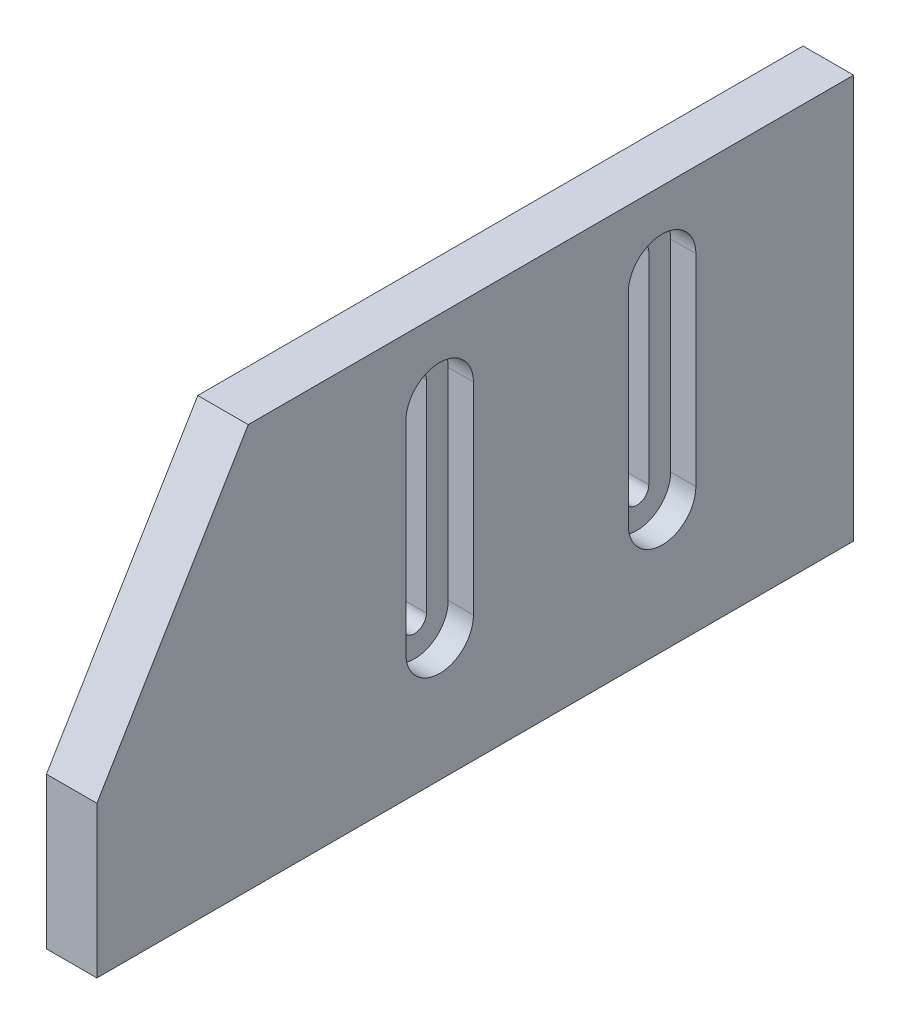
SolidWorks part; units mm, degrees
ref_plane "Front Plane" through (0, 0, 0) normal (0, 0, 1) x (1, 0, 0)
ref_plane "Top Plane" through (0, 0, 0) normal (0, 1, 0) x (1, 0, 0)
ref_plane "Right Plane" through (0, 0, 0) normal (1, 0, 0) x (0, 0, -1)
sketch "Sketch2" plane through (0, 0, 0) normal (1, 0, 0) x (0, 0, -1)
  line L0 (-38.1, 25.4) -> (-57.15, -6.35)
  line L1 (38.1, -25.4) -> (-38.1, -25.4)
  line L2 (38.1, -25.4) -> (38.1, 25.4)
  line L3 (38.1, 25.4) -> (-38.1, 25.4)
  line L4 (-38.1, -25.4) -> (-38.1, 25.4)
  line L5 (38.1, -25.4) -> (-38.1, 25.4) construction
  line L6 (38.1, 25.4) -> (-38.1, -25.4) construction
  line L7 (-57.15, -6.35) -> (-57.15, -25.4)
  line L8 (-57.15, -25.4) -> (-38.1, -25.4)
  dimension "D1" = 76.2
  dimension "D2" = 50.8
  dimension "D3" = 19.05
  dimension "D4" = 19.05
extrude "Boss-Extrude2" add sketch "Sketch2" along normal mid plane 6.35 contours L7 L8 L4 L0 | L4 L1 L2 L3 region at (0, -6.7348, 46.1818) region at (0, 0, 0)
sketch "Sketch3" plane through (3.175, 0, 0) normal (1, 0, 0) x (0, 0, -1)
  line L0 (-14, -9.525) -> (-14, 15.875) construction
  line L3 (-15.5, -9.525) -> (-15.5, 15.875)
  line L6 (-12.5, -9.525) -> (-12.5, 15.875)
  line L7 (14, -9.525) -> (14, 15.875) construction
  line L8 (12.5, -9.525) -> (12.5, 15.875)
  line L9 (15.5, -9.525) -> (15.5, 15.875)
  line L11 (-18.25, -9.525) -> (-18.25, 15.875)
  line L12 (-9.75, -9.525) -> (-9.75, 15.875)
  line L13 (9.75, -9.525) -> (9.75, 15.875)
  line L14 (18.25, -9.525) -> (18.25, 15.875)
  line L15 (-14, 3.175) -> (14, 3.175) construction
  line L16 (0, 3.175) -> (0, 0) construction
  line L17 (38.1, 25.4) -> (-38.1, 25.4) construction
  arc A4 (-15.5, -9.525) -> (-12.5, -9.525) centre (-14, -9.525) ccw
  arc A5 (-12.5, 15.875) -> (-15.5, 15.875) centre (-14, 15.875) ccw
  arc A6 (12.5, -9.525) -> (15.5, -9.525) centre (14, -9.525) ccw
  arc A7 (15.5, 15.875) -> (12.5, 15.875) centre (14, 15.875) ccw
  arc A8 (-9.75, 15.875) -> (-18.25, 15.875) centre (-14, 15.875) ccw
  arc A9 (-18.25, -9.525) -> (-9.75, -9.525) centre (-14, -9.525) ccw
  arc A10 (18.25, 15.875) -> (9.75, 15.875) centre (14, 15.875) ccw
  arc A11 (9.75, -9.525) -> (18.25, -9.525) centre (14, -9.525) ccw
  point P2 (-14, 3.175)
  point P7 (14, 3.175)
  point P16 (0, 0)
  dimension "D1" = 3
  dimension "D5" = 8.5
  dimension "D2" = 28
  dimension "D4" = 25.4
  dimension "D3" = 9.525
extrude "Cut-Extrude1" cut sketch "Sketch3" against normal through all both and the other way through all contours L6 A5 L3 A4 | L9 A7 L8 A6 region at (3.175, 3.175, 14) region at (3.175, 3.175, -14)
extrude "Cut-Extrude3" cut sketch "Sketch3<3>" against normal blind 3.175
sketch "Sketch3<3>" plane through (3.175, 0, 0) normal (1, 0, 0) x (0, 0, -1) same geometry as "Sketch3"
sketch "Sketch4" plane through (0, -25.4, 0) normal (0, -1, 0) x (1, 0, 0)
  circle A0 centre (0, 25.4) radius 1.27
  circle A2 centre (0, 0) radius 1.27
  circle A3 centre (0, -25.4) radius 1.27
  circle A4 centre (0, 34.925) radius 1.27
  circle A5 centre (0, 44.45) radius 1.27
  point P11 (0, 34.925)
  dimension "D1" = 2.54
  dimension "D3" = 3
  dimension "D2" = 25.4
  dimension "D4" = 9.525
  dimension "D5" = 9.525
extrude "Cut-Extrude2" cut sketch "Sketch4" against normal blind 15.24 and the other way through all
equation "\"D1@Sketch3\"=3mm"
equation "\"D5@Sketch3\"=8.5mm"
